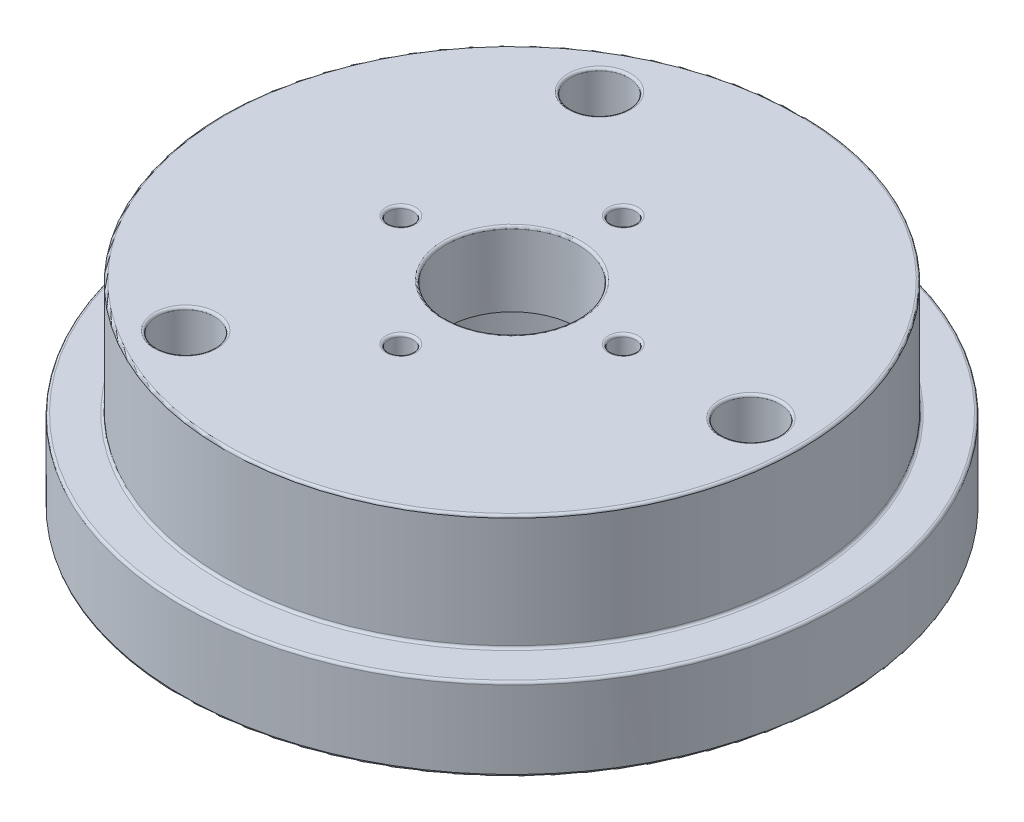
SolidWorks part; units mm, degrees
material "Cast Alloy Steel"
ref_plane "Front Plane" through (0, 0, 0) normal (0, 0, 1) x (1, 0, 0)
ref_plane "Top Plane" through (0, 0, 0) normal (0, 1, 0) x (1, 0, 0)
ref_plane "Right Plane" through (0, 0, 0) normal (1, 0, 0) x (0, 0, -1)
sketch "Sketch1" plane through (0, 0, 0) normal (0, 0, 1) x (1, 0, 0)
  line L0 (0, 0) -> (-20, 0)
  line L1 (-20, 0) -> (-20, 5)
  line L2 (-20, 5) -> (-17.5, 5)
  line L3 (-17.5, 5) -> (-17.5, 12)
  line L4 (-17.5, 12) -> (0, 12)
  line L5 (0, 12) -> (0, 0)
  dimension "D1" = 20
  dimension "D2" = 5
  dimension "D3" = 12
  dimension "D4" = 17.5
revolve "Revolve1" add sketch "Sketch1" angle 360 about L5
sketch "Sketch2" plane through (0, 0, 0) normal (0, -1, 0) x (1, 0, 0)
  circle A0 centre (0, 0) radius 10
  circle A1 centre (14.5, 0) radius 1.75
  circle A2 centre (-7.25, -12.5574) radius 1.75
  circle A3 centre (-7.25, 12.5574) radius 1.75
  circle A4 centre (0, 0) radius 20 construction
  circle A5 centre (0, 0) radius 4
  circle A6 centre (6.75, 0) radius 0.75
  circle A7 centre (0, -6.75) radius 0.75
  circle A8 centre (-6.75, 0) radius 0.75
  circle A9 centre (0, 6.75) radius 0.75
  point P11 (0, 0)
  point P24 (0, 0)
  dimension "D1" = 20
  dimension "D2" = 3.5
  dimension "D5" = 8
  dimension "D6" = 1.5
  dimension "D3" = 14.5
  dimension "D4" = 3
  dimension "D7" = 6.75
  dimension "D8" = 4
extrude "Cut-Extrude1" cut sketch "Sketch2" against normal through all contours A3 | A2 | A1 | A5 | A8 | A9 | A7 | A6 region at (14.5, 0, 0) region at (-7.25, 0, -12.5574) region at (-7.25, 0, 12.5574) region at (0, 0, 0) region at (6.75, 0, 0) region at (0, 0, -6.75) region at (-6.75, 0, 0) region at (0, 0, 6.75)
extrude "Cut-Extrude2" cut sketch "Sketch2<3>" against normal blind 7.5 contours A0
sketch "Sketch2<3>" plane through (0, 0, 0) normal (0, -1, 0) x (1, 0, 0) same geometry as "Sketch2"
fillet "Fillet1" radius 0.15 16 edges at (-20, 0, 0) (16.25, 0, 0) (-5.5, 0, -12.5574) (-5.5, 0, 12.5574) (10, 0, 0) (-17.5, 5, 0) (-20, 5, 0) (-17.5, 12, 0) (-6, 12, 0) (4, 12, 0) (16.25, 12, 0) (-5.5, 12, -12.5574) (0.75, 12, 6.75) (0.75, 12, -6.75) (7.5, 12, 0) (-5.5, 12, 12.5574)
